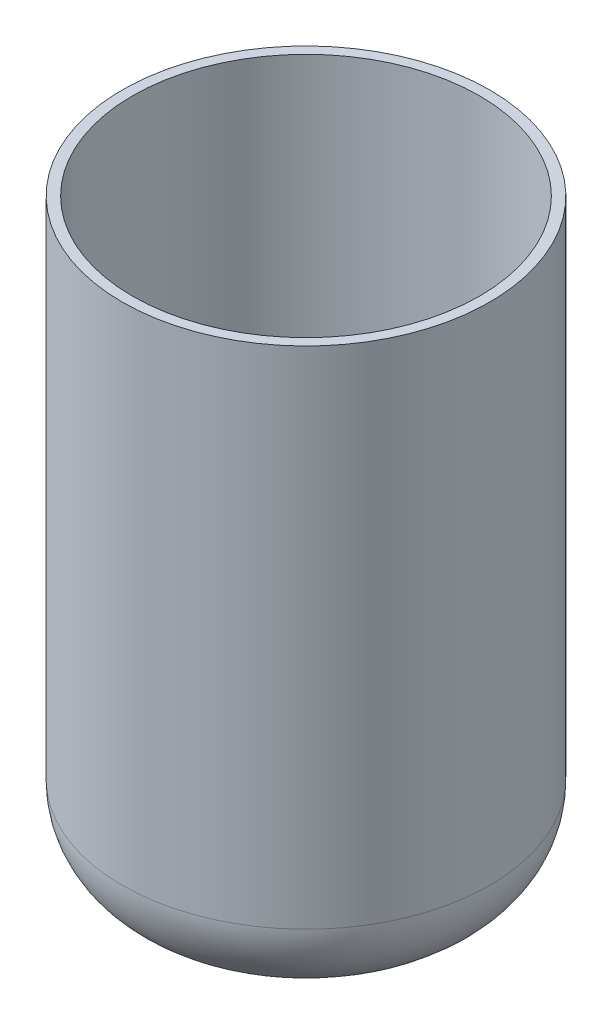
SolidWorks part; units mm, degrees
ref_plane "Front" through (0, 0, 0) normal (0, 0, 1) x (1, 0, 0)
ref_plane "Top" through (0, 0, 0) normal (0, 1, 0) x (1, 0, 0)
ref_plane "Right" through (0, 0, 0) normal (1, 0, 0) x (0, 0, -1)
sketch "Outside Profile_Sketch" plane through (0, 0, 0) normal (0, 0, 1) x (1, 0, 0)
  line L0 (0, 0) -> (0, -64.1658) construction
  line L1 (0, 0) -> (-18, 0)
  line L2 (-18, 0) -> (-18, -55.9)
  line L3 (-18, -55.9) -> (-4.5, -58.9)
  line L5 (-4.5, -58.9) -> (0, -58.9)
  line L6 (0, -58.9) -> (0, 0)
  dimension "Top Radius Loc" = 55.9
  dimension "Bot Radius Loc" = 58.9
  dimension "Taper" = 90
  dimension "Top Dia" = 36
  dimension "Bot Dia" = 9
revolve "Outside Profile" add sketch "Outside Profile_Sketch" angle 360 about L0
sketch "Neck_Sketch" plane through (0, 0, 0) normal (0, 1, 0) x (1, 0, 0)
  circle A0 centre (0, 0) radius 4.5
  dimension "Dia" = 9
extrude "Neck" add sketch "Neck_Sketch" against normal blind 61
fillet "Top Round" radius 8 1 edges at (0, -55.9, 18)
fillet "Bottom Round" [suppressed] radius 0.5
fillet "Blend" radius 0.5 1 edges at (0, -58.9, -4.5)
ref_plane "Rib Plane" [suppressed] through (0, -1.5, 0) normal (0, 1, 0) x (-1, 0, 0)
revolve "Shell" cut sketch "Shell_Sketch" angle 360 about L2
sketch "Shell_Sketch" plane through (0, 0, 0) normal (0, 0, 1) x (1, 0, 0)
  line L0 (0, -61) -> (0, -59.3011) construction
  line L2 (0, 0) -> (0, -96.8398) construction
  line L3 (0, -61) -> (0, -59.3011) construction
  line L5 (-4.2831, -57.9238) -> (0, -57.9238)
  line L6 (0, -57.9238) -> (0, 0)
  line L7 (-17, -55.0978) -> (-4.2831, -57.9238)
  line L8 (-17, 0) -> (-17, -55.0978)
  line L9 (-11.5185, -56.3159) -> (-4.2831, -57.9238)
  line L10 (-17, 0) -> (-17, -49.4826)
  line L11 (0, 0) -> (-17, 0)
  arc A0 (-17, -49.4826) -> (-11.5185, -56.3159) centre (-10, -49.4826) ccw
  arc A1 (-18, -49.4826) -> (-11.7354, -57.2921) centre (-10, -49.4826) ccw construction
  dimension "Offset" = 1
sketch "Rib_Sketch" [suppressed] plane through (0, -1.5, 0) normal (0, 1, 0) x (-1, 0, 0)
  line L1 (1.5, 0) -> (-1.5, 0)
  line L2 (1.5, 0) -> (1.5, 13.0138)
  line L4 (-1.5, 0) -> (-1.5, 13.0138)
  circle A2 centre (0, 0) radius 13.1
  arc A3 (1.5, 13.0138) -> (-1.5, 13.0138) centre (0, 0) ccw
  dimension "Width" = 4
  dimension "Offset" = 0.6
extrude "Rib" [suppressed] add sketch "Rib_Sketch" against normal blind 9
chamfer "Rib Cham" [suppressed] distance 0.25 angle 45
pattern_circular "Rib Pat" [suppressed] count 12 over 360 about axis through (0, 0, 0) along (0, -1, 0)
sketch "Rib Ring_Sketch" [suppressed] plane through (0, -1.5, 0) normal (0, 1, 0) x (-1, 0, 0)
  circle A0 centre (0, 0) radius 18.6
  circle A1 centre (0, 0) radius 18
  arc A2 (-16.9128, -7.7405) -> (-15.1599, -10.7767) centre (0, 0) ccw construction
  arc A3 (-16.4919, -7.2122) -> (-14.4919, -10.6763) centre (0, 0) ccw construction
extrude "Rib Ring" [suppressed] add sketch "Rib Ring_Sketch" along normal up to surface (1.5 mm away) up to face at (-17, 0, 0)
sketch "Metal Deform_Sketch" [suppressed] plane through (0, 0, 0) normal (0, 1, 0) x (-1, 0, 0)
  line L0 (0, 0) -> (0, 27.244) construction
  line L1 (-11, 30.316) -> (-12.2087, 28.2225)
  line L2 (11, 30.316) -> (12.2087, 28.2225)
  circle A1 centre (0, 0) radius 30.75 construction
  circle A2 centre (0, 0) radius 32.25
  arc A3 (11, 30.316) -> (-11, 30.316) centre (0, 0) ccw
  arc A4 (12.2087, 28.2225) -> (-12.2087, 28.2225) centre (0, 0) ccw
  dimension "Angle" = 30
  dimension "Width" = 16
  dimension "Offset" = 1
extrude "Metal Deform" [suppressed] add sketch "Metal Deform_Sketch" against normal blind 27
chamfer "Metal Deform Cham" [suppressed] distance 1 angle 35
fillet "Metal Deform Radius" [suppressed] radius 4
sketch "Release_Sketch" [suppressed] plane through (0, 0, 0) normal (0, 0, 1) x (1, 0, 0)
  line L0 (11, 0) -> (-11, 0) construction
  line L2 (-11, -29.131) -> (-11, 0) construction
  line L3 (11, 0) -> (-11, 0)
  line L4 (8.7765, -26.1484) -> (0.7765, -28.2919)
  line L5 (-11, -23.2506) -> (-11, 0)
  line L6 (0, 0) -> (0, -40.3189) construction
  line L7 (0, -119.5) -> (0, -118.4822) construction
  line L8 (-8.7765, -26.1484) -> (-0.7765, -28.2919)
  line L9 (-7.6213, -31.9497) -> (7.6213, -31.9497) construction
  line L10 (11, -23.2506) -> (11, 0)
  arc A0 (0.7765, -28.2919) -> (-0.7765, -28.2919) centre (0, -25.3942) cw
  arc A1 (-11, -23.2506) -> (-8.7765, -26.1484) centre (-8, -23.2506) ccw
  arc A2 (11, -23.2506) -> (8.7765, -26.1484) centre (8, -23.2506) cw
  point P15 (0, -28.5)
  point P18 (-11, -25.5526)
  point P21 (11, -25.5526)
  dimension "Radius" = 3
  dimension "Length" = 23.5
  dimension "Angle" = 15
extrude "Release" [suppressed] add sketch "Release_Sketch" along normal blind 30.5
sketch "Release Grip_Sketch" [suppressed] plane through (0, 0, 38) normal (0, 0, 1) x (1, 0, 0)
  line L12 (0, 0) -> (0, -35.5347) construction
  line L13 (0, -37.7801) -> (0, -23.4397) construction
  line L14 (0.2588, -21.7014) -> (9.7412, -19.1606)
  line L15 (11, -23.2506) -> (11, 0) construction
  line L19 (-11, 0) -> (-11, -23.2506) construction
  line L20 (-9.7412, -19.1606) -> (-0.2588, -21.7014)
  line L21 (0.7765, -28.2919) -> (8.7765, -26.1484) construction
  line L24 (11, -23.2506) -> (11, 0)
  line L25 (11, 0) -> (-11, 0)
  line L26 (-11, 0) -> (-11, -23.2506)
  line L27 (-8.7765, -26.1484) -> (-0.7765, -28.2919)
  line L28 (0.7765, -28.2919) -> (8.7765, -26.1484)
  line L29 (11, -23.2506) -> (11, -20.1265)
  line L31 (-11, -20.1265) -> (-11, -23.2506)
  line L32 (-8.7765, -26.1484) -> (-0.7765, -28.2919)
  line L33 (0.7765, -28.2919) -> (8.7765, -26.1484)
  arc A0 (-9.7412, -19.1606) -> (-11, -20.1265) centre (-10, -20.1265) ccw
  arc A1 (-0.2588, -21.7014) -> (0.2588, -21.7014) centre (0, -20.7354) ccw
  arc A2 (11, -20.1265) -> (9.7412, -19.1606) centre (10, -20.1265) ccw
  arc A3 (-11, -23.2506) -> (-8.7765, -26.1484) centre (-8, -23.2506) ccw
  arc A4 (-0.7765, -28.2919) -> (0.7765, -28.2919) centre (0, -25.3942) ccw
  arc A5 (8.7765, -26.1484) -> (11, -23.2506) centre (8, -23.2506) ccw
  arc A6 (-11, -23.2506) -> (-8.7765, -26.1484) centre (-8, -23.2506) ccw
  arc A7 (-0.7765, -28.2919) -> (0.7765, -28.2919) centre (0, -25.3942) ccw
  arc A8 (8.7765, -26.1484) -> (11, -23.2506) centre (8, -23.2506) ccw
  point P24 (-11, -18.8233)
  point P32 (0, -21.7707)
  point P35 (11, -18.8233)
  dimension "Radius" = 1
  dimension "Width" = 5.5
  dimension "D2" = 0
extrude "Release Grip" [suppressed] cut sketch "Release Grip_Sketch" against normal blind 4 flip side to cut
ref_plane "Level Plane" [suppressed] through (0, 0, 38.4) normal (0, 0, 1) x (1, 0, 0)
sketch "Level Boss_Sketch" [suppressed] plane through (0, 0, 38.4) normal (0, 0, 1) x (1, 0, 0)
  line L0 (-21, 0) -> (-21, -99.2188) construction
  line L1 (-28.5, -2.1) -> (-13.5, -2.1)
  line L2 (-28.5, -2.1) -> (-28.5, -111.1)
  line L3 (-28.5, -111.1) -> (-13.5, -111.1)
  line L4 (-13.5, -2.1) -> (-13.5, -111.1)
  line L6 (30.75, 0) -> (-30.75, 0) construction
  dimension "Loc Y" = 2.1
  dimension "Length" = 87.5
  dimension "Width" = 13
  dimension "Loc X" = 16
extrude "Level Boss" [suppressed] add sketch "Level Boss_Sketch" against normal blind 18
chamfer "Level Boss Cham" [suppressed] distance 2 angle 45
sketch "Level Bolts_Sketch" [suppressed] plane through (0, 0, 38.4) normal (0, 0, 1) x (1, 0, 0)
  line L2 (-21, -6.35) -> (-21, -106.85) construction
  line L3 (-28.5, -2.1) -> (-28.5, -111.1) construction
  line L4 (-13.5, -111.1) -> (-13.5, -2.1) construction
  line L5 (-39.6472, -56.6) -> (52.5506, -56.6) construction
  line L6 (-26.5, -111.1) -> (-15.5, -111.1) construction
  line L7 (-15.5, -2.1) -> (-26.5, -2.1) construction
  circle A0 centre (-21, -6.35) radius 3.5
  circle A1 centre (-21, -106.85) radius 3.5
  dimension "Dia" = 7
  dimension "C2C" = 78.5
extrude "Level Bolts" [suppressed] add sketch "Level Bolts_Sketch" along normal blind 0.7
sketch "Level Bolt Slots_Sketch" [suppressed] plane through (0, 0, 39.1) normal (0, 0, 1) x (1, 0, 0)
  line L0 (-21, 0.1201) -> (-21, -12.8201) construction
  line L1 (-25.4487, -6.35) -> (-16.5513, -6.35) construction
  line L2 (-21.5, -6.85) -> (-21.5, -8.4)
  line L3 (-21.5, -4.3) -> (-20.5, -4.3)
  line L4 (-21.5, -4.3) -> (-21.5, -5.85)
  line L5 (-21.5, -8.4) -> (-20.5, -8.4)
  line L6 (-20.5, -4.3) -> (-20.5, -5.85)
  line L7 (-23.05, -5.85) -> (-21.5, -5.85)
  line L8 (-23.05, -5.85) -> (-23.05, -6.85)
  line L9 (-23.05, -6.85) -> (-21.5, -6.85)
  line L10 (-18.95, -5.85) -> (-18.95, -6.85)
  line L11 (-20.5, -5.85) -> (-18.95, -5.85)
  line L12 (-20.5, -6.85) -> (-18.95, -6.85)
  line L13 (-20.5, -6.85) -> (-20.5, -8.4)
  line L14 (-67.9626, -56.6) -> (49.3154, -56.6) construction
  line L15 (-20.5, -106.35) -> (-20.5, -104.8)
  line L16 (-20.5, -106.35) -> (-18.95, -106.35)
  line L17 (-20.5, -107.35) -> (-18.95, -107.35)
  line L18 (-18.95, -107.35) -> (-18.95, -106.35)
  line L19 (-23.05, -106.35) -> (-21.5, -106.35)
  line L20 (-23.05, -107.35) -> (-23.05, -106.35)
  line L21 (-23.05, -107.35) -> (-21.5, -107.35)
  line L22 (-20.5, -108.9) -> (-20.5, -107.35)
  line L23 (-21.5, -104.8) -> (-20.5, -104.8)
  line L24 (-21.5, -108.9) -> (-21.5, -107.35)
  line L25 (-21.5, -108.9) -> (-20.5, -108.9)
  line L26 (-21.5, -106.35) -> (-21.5, -104.8)
  dimension "Width" = 1
  dimension "Length" = 4.1
dome "Level Bolts Dome1" [suppressed] faces to dome 1 distance 1.9 parameters "Height"=1.9
dome "Level Bolts Dome2" [suppressed] faces to dome 1 distance 1.9 parameters "Height"=1.9
extrude "Level Bolt Slots" [suppressed] cut sketch "Level Bolt Slots_Sketch" along normal through all
sketch "Level Pocket_Sketch" [suppressed] plane through (0, 0, 38.4) normal (0, 0, 1) x (1, 0, 0)
  line L0 (-13.5, -111.1) -> (-13.5, -2.1) construction
  line L1 (-13.5, -21.85) -> (-21.5, -21.85)
  line L2 (-13.5, -21.85) -> (-13.5, -91.35)
  line L3 (-13.5, -91.35) -> (-21.5, -91.35)
  line L4 (-21.5, -21.85) -> (-21.5, -91.35)
  line L5 (-13.5, -56.6) -> (-33.0631, -56.6) construction
  line L6 (-15.5, -2.1) -> (-26.5, -2.1) construction
  line L7 (-26.5, -111.1) -> (-15.5, -111.1) construction
  dimension "Length" = 47.5
  dimension "Width" = 8
extrude "Level Pocket" [suppressed] cut sketch "Level Pocket_Sketch" against normal blind 5
sketch "Level Indicator_Sketch" [suppressed] plane through (0, -91.35, 0) normal (0, 1, 0) x (-1, 0, 0)
  line L3 (34.2045, 35.9) -> (12.0907, 35.9) construction
  line L4 (15.5, 38.4) -> (26.5, 38.4) construction
  line L5 (13.5, 33.4) -> (21.5, 33.4) construction
  line L6 (17.5, 35.9) -> (17.5, 43.3347) construction
  line L7 (21.5, 33.4) -> (21.5, 38.4) construction
  line L8 (13.5, 27.6281) -> (13.5, 36.4) construction
  circle A0 centre (17.5, 35.9) radius 1.5
  dimension "Dia" = 3
extrude "Level Indicator" [suppressed] add sketch "Level Indicator_Sketch" along normal up to surface (69.5 mm away)
ref_plane "Site Plane" [suppressed] through (0, 0, 0) normal (-0.7071, 0, 0.7071) x (0.7071, 0, 0.7071)
sketch "Site_Sketch" [suppressed] plane through (0, 0, 0) normal (-0.7071, 0, 0.7071) x (0.7071, 0, 0.7071)
  line L0 (0, 0) -> (0, -61.3474) construction
  line L1 (0, -119.5) -> (0, -118.4822) construction
  line L2 (30.75, 0) -> (-30.75, 0) construction
  line L3 (-2, -7) -> (2, -7)
  line L4 (-6, -11) -> (-6, -88)
  line L5 (-2, -92) -> (2, -92)
  line L6 (6, -11) -> (6, -88)
  arc A0 (-2, -92) -> (-6, -88) centre (-2, -88) cw
  arc A1 (6, -88) -> (2, -92) centre (2, -88) cw
  arc A2 (6, -11) -> (2, -7) centre (2, -11) ccw
  arc A3 (-6, -11) -> (-2, -7) centre (-2, -11) cw
  point P13 (-6, -92)
  point P18 (6, -7)
  point P21 (-6, -7)
  dimension "Radius" = 4
  dimension "Width" = 10
  dimension "Loc Y" = 7
  dimension "Length" = 50
extrude "Site" [suppressed] cut sketch "Site_Sketch" against normal through all
pattern_circular "Site Pat" [suppressed] count 4 over 360 about axis through (0, 0, 0) along (0, -1, 0)
